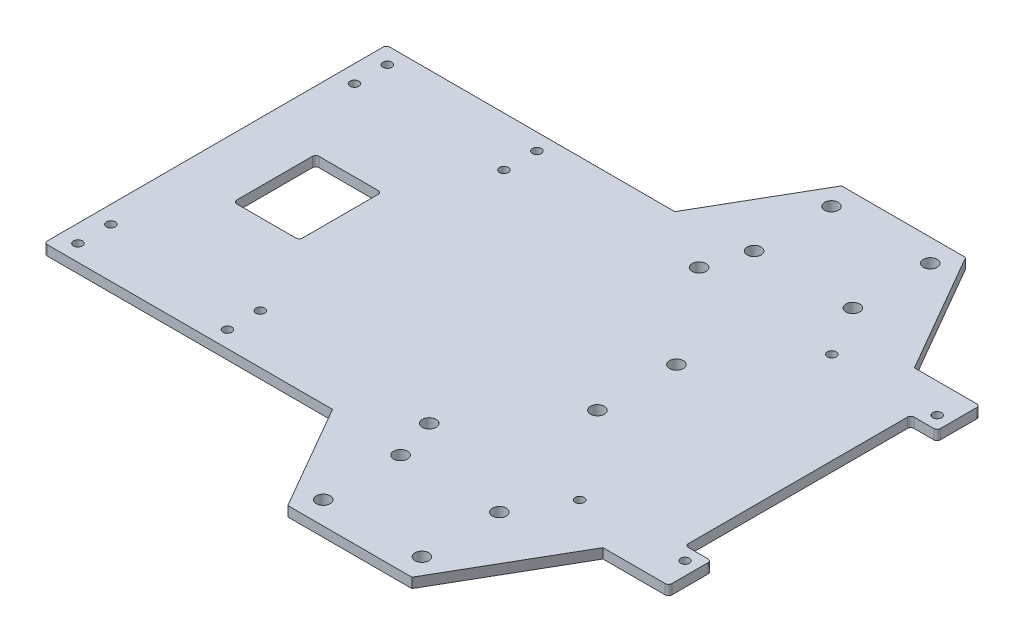
SolidWorks part; units mm, degrees
material "Acrylic (Medium-high impact)"
ref_plane "Front Plane" through (0, 0, 0) normal (0, 0, 1) x (1, 0, 0)
ref_plane "Top Plane" through (0, 0, 0) normal (0, 1, 0) x (1, 0, 0)
ref_plane "Right Plane" through (0, 0, 0) normal (1, 0, 0) x (0, 0, -1)
sketch "Sketch1" plane through (0, 0, 0) normal (0, 1, 0) x (1, 0, 0)
  line L0 (0, 52) -> (0, -52)
  line L12 (0, 52) -> (87.6171, 52)
  line L13 (87.6171, 52) -> (106.15, 84.1)
  line L14 (106.15, 84.1) -> (143.85, 84.1)
  line L15 (143.85, 84.1) -> (165.0965, 47.3)
  line L16 (165.0965, 47.3) -> (185, 47.3)
  line L17 (185, 47.3) -> (185, -47.3)
  line L18 (185, -47.3) -> (165.0965, -47.3)
  line L19 (165.0965, -47.3) -> (143.85, -84.1)
  line L20 (143.85, -84.1) -> (106.15, -84.1)
  line L21 (106.15, -84.1) -> (87.6171, -52)
  line L22 (87.6171, -52) -> (0, -52)
  line L23 (125, 84.1) -> (125, -84.1) construction
  point P12 (125, 0)
  point P15 (0, 0)
  point P23 (185, 0)
  dimension "D1" = 104
  dimension "D2" = 37.7
  dimension "D3" = 32.1
  dimension "D4" = 120
  dimension "D5" = 143.85
  dimension "D6" = 185
  dimension "D7" = 94.6
extrude "Boss-Extrude1" add sketch "Sketch1" along normal blind 3
sketch "Sketch2" plane through (0, 3, 0) normal (0, 1, 0) x (1, 0, 0)
  line L0 (87.6171, 52) -> (0, 52) construction
  line L1 (0, 52) -> (0, -52) construction
  circle A0 centre (5.3, 47) radius 1.35
  circle A1 centre (5.3, 37) radius 1.35
  circle A2 centre (50.7, 47) radius 1.35
  circle A3 centre (50.7, 37) radius 1.35
  dimension "D3" = 2.7
  dimension "D1" = 5
  dimension "D2" = 5.3
  dimension "D4" = 10
  dimension "D5" = 45.4
extrude "Motor Clevis Holes" cut sketch "Sketch2" against normal through all
mirror "Motor Clevis Holes Mirror" about plane through (0, 0, 0) normal (0, 0, 1) of "Motor Clevis Holes"
sketch "Sketch3" plane through (0, 3, 0) normal (0, 1, 0) x (1, 0, 0)
  line L0 (165.0965, -47.3) -> (185, -47.3) construction
  line L1 (185, -47.3) -> (185, 47.3) construction
  circle A0 centre (181, -38.3) radius 1.35
  circle A1 centre (149, -38.3) radius 1.35
  dimension "D1" = 2.7
  dimension "D2" = 9
  dimension "D3" = 4
  dimension "D4" = 32
extrude "Servo Clevis Holes" cut sketch "Sketch3" against normal through all
mirror "Servo Clevis Holes Mirror" about plane through (0, 0, 0) normal (0, 0, 1) of "Servo Clevis Holes"
sketch "Sketch4" plane through (0, 3, 0) normal (0, 1, 0) x (1, 0, 0)
  line L2 (0, 52) -> (0, -52) construction
  line L3 (0, -52) -> (87.6171, -52) construction
  circle A2 centre (128.1, -12) radius 2.1
  dimension "D3" = 40
  dimension "D1" = 4.2
  dimension "D2" = 128.1
extrude "Bucket Hole" cut sketch "Sketch4" against normal through all
mirror "Bucket Hole Mirror" about plane through (0, 0, 0) normal (0, 0, 1) of "Bucket Hole"
sketch "Sketch5" plane through (0, 3, 0) normal (0, 1, 0) x (1, 0, 0)
  line L0 (0, -52) -> (87.6171, -52) construction
  line L1 (0, 52) -> (0, -52) construction
  circle A0 centre (110, -53.7) radius 2.1
  circle A1 centre (110, -77.2) radius 2.1
  circle A2 centre (140, -77.2) radius 2.1
  circle A3 centre (140, -53.7) radius 2.1
  dimension "D3" = 4.2
  dimension "D1" = 1.7
  dimension "D2" = 110
  dimension "D4" = 23.5
  dimension "D5" = 30
extrude "Caster Holes" cut sketch "Sketch5" against normal through all
mirror "Caster Holes Mirror" about plane through (0, 0, 0) normal (0, 0, 1) of "Caster Holes"
sketch "Sketch6" plane through (0, 3, 0) normal (0, 1, 0) x (1, 0, 0)
  line L1 (185, -47.3) -> (185, 47.3) construction
  line L2 (165.0965, -47.3) -> (185, -47.3) construction
  line L3 (185, 34.3) -> (177, 34.3)
  line L4 (185, 34.3) -> (185, -34.3)
  line L5 (185, -34.3) -> (177, -34.3)
  line L6 (177, 34.3) -> (177, -34.3)
  point P8 (185, 0)
  point P16 (185, 0)
  point P17 (170, -2.1662)
  point P20 (170, -2.5528)
  point P21 (170, -23.4545)
  point P22 (0, 0)
  point P24 (170, 29.5058)
  dimension "D1" = 8
  dimension "D7" = 13
extrude "Front Notch" cut sketch "Sketch6" against normal through all
fillet "Fillet2" radius 1 8 edges at (185, 1.5, 47.3) (185, 1.5, 34.3) (177, 1.5, 34.3) (177, 1.5, -34.3) (185, 1.5, -34.3) (185, 1.5, -47.3) (0, 1.5, -52) (0, 1.5, 52)
sketch "Sketch9" plane through (0, 3, 0) normal (0, 1, 0) x (1, 0, 0)
  line L0 (0, 51) -> (0, -51) construction
  line L1 (106, -41) -> (106, 41) construction
  circle A0 centre (106, 41) radius 2.1
  circle A2 centre (106, -41) radius 2.1
  point P6 (106, 0)
  dimension "D3" = 4.2
  dimension "D1" = 106
  dimension "D2" = 82
extrude "Color Sensor Bracket Holes" cut sketch "Sketch9" against normal through all
sketch "Sketch10" plane through (0, 3, 0) normal (0, 1, 0) x (1, 0, 0)
  line L1 (18, -12.5) -> (38, -12.5)
  line L2 (18, -12.5) -> (18, 12.5)
  line L3 (18, 12.5) -> (38, 12.5)
  line L4 (38, -12.5) -> (38, 12.5)
  line L5 (18, -12.5) -> (38, 12.5) construction
  line L6 (18, 12.5) -> (38, -12.5) construction
  point P0 (28, 0)
  point P3 (28, 0)
  dimension "D1" = 28
  dimension "D2" = 20
  dimension "D3" = 25
extrude "Motor Routing Pocket" cut sketch "Sketch10" against normal through all
fillet "Fillet3" radius 1 4 edges at (18, 1.5, 12.5) (38, 1.5, 12.5) (38, 1.5, -12.5) (18, 1.5, -12.5)
